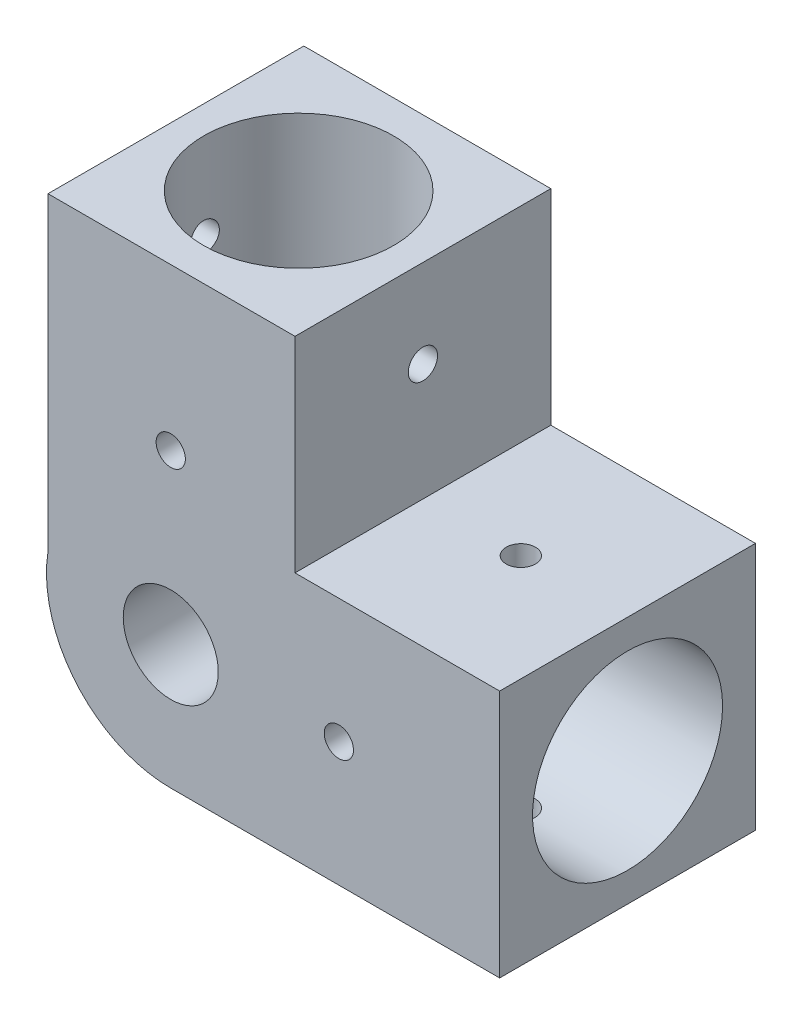
SolidWorks part; units mm, degrees
ref_plane "Спереди" through (0, 0, 0) normal (0, 0, 1) x (1, 0, 0)
ref_plane "Сверху" through (0, 0, 0) normal (0, 1, 0) x (1, 0, 0)
ref_plane "Справа" through (0, 0, 0) normal (1, 0, 0) x (0, 0, -1)
sketch "Эскиз1" plane through (0, 0, 0) normal (0, 0, 1) x (1, 0, 0)
  circle A0 centre (0, 0) radius 6.5
  circle A1 centre (0, 0) radius 17
extrude "Бобышка-Вытянуть2" add sketch "Эскиз1" along normal blind 35
ref_plane "Плоскость4" through (0, 45.0332, 0) normal (0, 1, 0) x (1, 0, 0)
sketch "Эскиз3" plane through (0, 45.0332, 0) normal (0, 1, 0) x (1, 0, 0)
  line L0 (17, -35) -> (17, 0) construction
  line L13 (-16.7953, 0) -> (17, 0)
  line L14 (-16.7953, 0) -> (-16.7953, -35)
  line L15 (-16.7953, -35) -> (17, -35)
  line L16 (17, 0) -> (17, -35)
  line L17 (-16.7953, 0) -> (-17, 0) construction
  line L18 (-17, 0) -> (-17, -35) construction
  line L19 (-16.7953, -35) -> (-17, -35) construction
  circle A1 centre (0, -17.5) radius 13
extrude "Бобышка-Вытянуть7" add sketch "Эскиз3" against normal blind 45
sketch "Эскиз4" plane through (0, 0, 0) normal (0, 0, -1) x (-1, 0, 0)
  circle A0 centre (0, 0) radius 6.5
sketch "Эскиз12" plane through (0, 0, 0) normal (0, 0, -1) x (-1, 0, 0)
  line L0 (0, 23) -> (0, 0) construction
  circle A3 centre (0, 23) radius 2
extrude "Вырез-Вытянуть11" cut sketch "Эскиз12" against normal blind 45
sketch "Эскиз15" plane through (-16.7953, 0, 0) normal (-1, 0, 0) x (0, 0, 1)
  line L0 (0, 0) -> (0, 33) construction
  line L1 (0, 33) -> (17.5, 33) construction
  circle A1 centre (17.5, 33) radius 2
extrude "Вырез-Вытянуть12" cut sketch "Эскиз15" against normal blind 45
sketch "Эскиз20" plane through (0, 45.0332, 0) normal (0, 1, 0) x (1, 0, 0)
  circle A3 centre (0, -17.5) radius 13
extrude "Вырез-Вытянуть18" cut sketch "Эскиз20" against normal blind 30
sketch "Эскиз25" plane through (0, 15.0332, 0) normal (0, 1, 0) x (1, 0, 0)
  circle A2 centre (0, -18) radius 13
extrude "Бобышка-Вытянуть10" add sketch "Эскиз25" along normal blind 2
sketch3d "Трехмерный эскиз3"
  point P0 (16.7518, -2.8944, 24.542)
sketch "Эскиз40" plane through (0, 45.0332, 0) normal (0, 1, 0) x (1, 0, 0)
  circle A0 centre (0, -17.5) radius 13
sketch "Эскиз50" plane through (0, 0, 35) normal (0, 0, 1) x (1, 0, 0)
  line L0 (0, 0) -> (0, 45.0332) construction
  line L1 (13, 45.0332) -> (-13, 45.0332) construction
  line L2 (0, 0) -> (45, 0) construction
  line L4 (0, -17) -> (45, -17)
  line L5 (0, -17) -> (0, 17)
  line L6 (0, 17) -> (45, 17)
  line L7 (45, -17) -> (45, 17)
extrude "Бобышка-Вытянуть12" add sketch "Эскиз50" against normal up to surface (35 mm away) up to face at (-2, 23, 0)
extrude "Вырез-Вытянуть22" cut sketch "Эскиз4" against normal through all both and the other way through all
sketch "Эскиз52" plane through (45, 0, 0) normal (1, 0, 0) x (0, 0, -1)
  line L0 (0, 0) -> (-35, 0) construction
  line L1 (-35, -17) -> (-35, 17) construction
  circle A0 centre (-17.5, 0) radius 13
extrude "Вырез-Вытянуть23" cut sketch "Эскиз52" against normal blind 28
sketch "Эскиз53" plane through (0, 17, 0) normal (0, 1, 0) x (1, 0, 0)
  line L0 (45, -17.5) -> (30.4, -17.5) construction
  line L1 (45, 0) -> (45, -35) construction
  circle A0 centre (30.4, -17.5) radius 2
extrude "Вырез-Вытянуть24" cut sketch "Эскиз53" against normal through all both and the other way through all
sketch "Эскиз54" plane through (0, 0, 35) normal (0, 0, 1) x (1, 0, 0)
  line L0 (0, 0) -> (0, 23) construction
  line L1 (0, 0) -> (23, 0) construction
  circle A0 centre (23, 0) radius 2
extrude "Вырез-Вытянуть25" cut sketch "Эскиз54" against normal through all both and the other way through all
sketch "Эскиз55" plane through (0, 0, 35) normal (0, 0, 1) x (1, 0, 0)
  line L0 (0, 0) -> (1.0999, 1.1851) construction
sketch "Эскиз56" plane through (0, 0, 0) normal (0, 0, -1) x (-1, 0, 0)
  line L0 (-0.5507, 12.4532) -> (0, 0) construction
  line L1 (0, 0) -> (2.3294, 0) construction
ref_plane "Плоскость5" through (17, 17, 35) normal (-1, 0, 0) x (0, 0, 1)
sketch "Эскиз57" plane through (0, 0, 0) normal (0, 0, -1) x (-1, 0, 0)
  circle A0 centre (0, 0) radius 11.5
extrude "Вырез-Вытянуть26" cut sketch "Эскиз57" against normal blind 7.5
